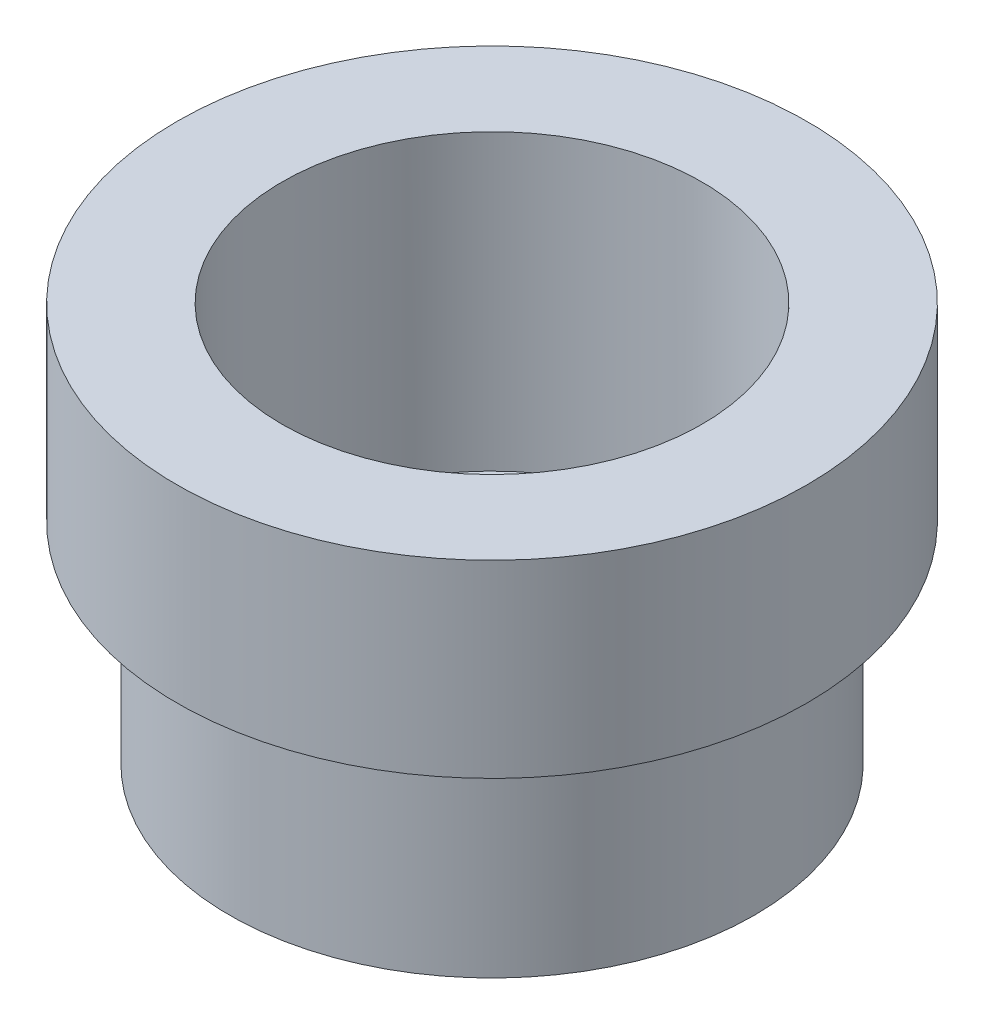
SolidWorks part; units mm, degrees
material "1060 Alloy"
ref_plane "Front" through (0, 0, 0) normal (0, 0, 1) x (1, 0, 0)
ref_plane "Top" through (0, 0, 0) normal (0, 1, 0) x (1, 0, 0)
ref_plane "Right" through (0, 0, 0) normal (1, 0, 0) x (0, 0, -1)
sketch "Sketch1" plane through (0, 0, 0) normal (0, 0, 1) x (1, 0, 0)
  line L0 (0, 0) -> (25, 0)
  line L1 (25, 0) -> (25, 20)
  line L2 (25, 20) -> (30, 20)
  line L3 (30, 20) -> (30, 38)
  line L6 (30, 38) -> (0, 38)
  line L7 (0, 38) -> (0, 0)
  dimension "D1" = 18
  dimension "D2" = 20
  dimension "D3" = 30
  dimension "D4" = 25
revolve "Revolve1" add sketch "Sketch1" angle 360 about L7
sketch "Sketch3" plane through (0, 38, 0) normal (0, 1, 0) x (1, 0, 0)
  circle A0 centre (0, 0) radius 10
  dimension "D1" = 20
extrude "bore through" cut sketch "Sketch3" against normal through all
sketch "Sketch5" plane through (0, 38, 0) normal (0, 1, 0) x (1, 0, 0)
  circle A0 centre (0, 0) radius 20
  dimension "D1" = 40
extrude "center cavity" cut sketch "Sketch5" against normal offset from surface (28 mm away) 10 up to face at (0, 0, 10)
sketch "m4 pattern alignment" plane through (0, 10, 0) normal (0, 1, 0) x (1, 0, 0)
  circle A0 centre (0, 0) radius 15 construction
  circle A1 centre (0, 15) radius 2.15
  point P3 (0, 15)
  point P4 (12.9904, 7.5)
  point P7 (12.9904, -7.5)
  point P8 (0, -15)
  point P9 (-12.9904, -7.5)
  point P10 (-12.9904, 7.5)
  point P11 (0, 0)
  dimension "D1" = 30
  dimension "D3" = 4.3
  dimension "D2" = 6
extrude "Cut-Extrude1" cut sketch "m4 pattern alignment" against normal through all
pattern_circular "CirPattern1" count 6 over 360 about axis through (0, 10, 0) along (0, -1, 0) of "Cut-Extrude1"
sketch "Sketch7" plane through (0, 10, 0) normal (0, 1, 0) x (1, 0, 0)
  circle A0 centre (0, 15) radius 4
extrude "Cut-Extrude2" cut sketch "Sketch7" against normal blind 4
pattern_circular "CirPattern2" count 6 over 360 about axis through (0, 10, 0) along (0, -1, 0) of "Cut-Extrude2"
equation "\"D1\"= \"motor mount plate thickness\""
equation "\"coupler motor shaft hole ID\"= 8mm"
equation "\"coupler OD\"= 17mm"
equation "\"coupler length\"= 25mm"
equation "\"square plate bolt pattern diameter\"= 3.5in"
equation "\"motor mount m4 screw hole diameter\"= 4mm"
equation "\"motor mount m4 head diameter\"= 7.25mm"
equation "\"motor mount m4 head depth\"= 4mm"
equation "\"motor mount plate thickness\"= 8mm + \"motor mount m4 head depth\""
equation "\"motor shaft pride\"= 32mm"
equation "\"motor mount m4 pattern diamater\"= 30mm"
equation "\"motor OD\"= 64mm"
equation "\"square plate bolt bore\"= \"m8 clearance\""
equation "\"square plate bolt head diameter\"= 13.5mm"
equation "\"motor to bearing plate distance\"= \"motor shaft pride\" + 2mm +\"coupler length\"/2"
equation "\"motor mount center bore\"= \"coupler OD\"+ 4mm"
equation "\"motor mount post radius\"= ( 3 * \"square plate bolt bore\" ) / 2"
equation "\"motor shaft diameter\"= 8mm"
equation "\"D1\"= 20mm"
equation "\"z\"= 8\t\t\t\t'number of blades"
equation "\"de\"= 0.43in\t\t\t'entrance eye diameter"
equation "\"de_length\"= 4mm\t\t'entrance eye consistent length"
equation "\"d_exit\"= 0.18in \t\t'throat aka d1"
equation "\"d2\"= 2.1in \t\t\t'outer diameter of the impeller"
equation "\"b2\"= .2in\t\t\t'tip height from disc surface at d2; slightly higher than d_exit"
equation "\"theta\"= 12\t\t\t'angle of blades from inner to outer "
equation "\"ae\"= 3.14*(\"de\"^2)/4\t\t'entrance eye area'"
equation "\"ce\"= 3.14*\"de\"\t\t'entrance eye circumference"
equation "\"av_ratio\"= .325\t\t'ratio of av/ae at N_s of 470, range is .275 to .375, .325 ideal. High ratio means bigger area means smaller blades"
equation "\"av\"= \"ae\"*\"av_ratio\"\t\t'area between just two blades"
equation "\"min blade thickness\"= .15in"
equation "\"diffuser cartridge OD\"=.75in"
equation "\"diffuser flange bolt pattern diameter\"= 1.4in"
equation "\"bearing OD\"= 30mm"
equation "\"bearing ID\"= 10mm"
equation "\"bearing depth\"= 9mm"
equation "\"bearing outer race thickness\"= 1mm"
equation "\"bearing inner race thickness\"= 1mm"
equation "\"bearing bore\"= \"bearing depth\" + 1mm"
equation "\"lower seal OD\"= .917in\t\t'this is https://www.mcmaster.com/#9281k121/=174001b"
equation "\"lower seal ID\"= .375in"
equation "\"lower seal depth\"= .625in + .218in"
equation "\"lower seal bore\"= \"lower seal depth\" + 1mm"
equation "\"upper seal OD\"= 1.125in\t'this is https://www.mcmaster.com/#5154t33/=173zuau, needs to be visually inspected before machining!"
equation "\"upper seal ID\"= 0.625in"
equation "\"upper seal depth\"= .25in\t'aka height; these values need to be confirmed by inspection!! We may want to compress the height."
equation "\"upper seal bore\"= \"upper seal depth\" + 1mm"
equation "\"big o-ring thickness\"= .139in"
equation "\"big o-ring OD\"= 2.734in"
equation "\"big o-ring ID\"= 3.012in"
equation "\"big o-ring groove depth\"= \"big o-ring thickness\"*4/5"
equation "\"impeller upper clearance\"= .5mm"
equation "\"impeller horizontal clearance\"= (\"d2\"*1.15 - \"d2\")/2 \t\t'clearance based on D2-D3 ratio for circular volute, ranges 1.15 to 1.2"
equation "\"impeller bottom clearance\"= .5mm"
equation "\"impeller base thickness\"= 2mm"
equation "\"impeller dowel diameter\"= 2mm"
equation "\"impeller bolt head depth\"= 4mm"
equation "\"impeller bolt stop depth\"= 3mm"
equation "\"impeller shaft bore depth\"= 12mm"
equation "\"impeller shaft bore\"= 8mm"
equation "\"impeller boss depth\"= \"impeller shaft bore depth\"+\"impeller bolt stop depth\"+\"impeller bolt head depth\"-\"impeller base thickness\""
equation "\"impeller boss diameter\"= \"upper seal ID\""
equation "\"impeller dowel length\"= 2mm*2 + \"impeller shaft bore\""
equation "\"square plate bolt head depth\"= 8mm"
equation "\"bearing plate stop ID\"= \"bearing OD\" - 4mm"
equation "\"bearing plate stop depth\"= 3mm"
equation "\"lower seal plate lip depth\"= 2mm"
equation "\"lower seal plate lip ID\"= \"lower seal OD\" - 3mm"
equation "\"lower seal plate thickness\"= \"lower seal plate lip depth\" + \"lower seal bore\""
equation "\"shaft coupler section diameter\"= 8mm"
equation "\"shaft coupler section length\"= \"motor to bearing plate distance\" - \"motor shaft pride\" - 2mm"
equation "\"shaft bearing section diameter\"= \"bearing ID\""
equation "\"shaft bearing section length\"= \"bearing plate stop depth\" + \"bearing depth\""
equation "\"shaft bearing stop diameter\"= \"bearing ID\" + 4mm"
equation "\"shaft bearing stop length\"= 3mm"
equation "\"shaft lower seal section diameter\"= \"lower seal ID\""
equation "\"shaft lower seal section length\"= \"lower seal plate thickness\" + 1mm"
equation "\"shaft impeller section diameter\"= \"impeller shaft bore\""
equation "\"upper seal plate lip ID\"= \"upper seal OD\" - 3mm"
equation "\"upper seal plate riser\"= 6.59mm \t\t'this number needs to be read from the housing file"
equation "\"upper seal plate pressure hole diameter\"= .125in\t'this is 1/8 drill "
equation "\"upper seal plate pressure tap diameter\"= .328125in \t'this is 21/64 drill for a 1/8 ANPT tap"
equation "\"upper seal plate pressure tap grip\"= 5mm\t\t'this is the area around the tap so it doesn't crack"
equation "\"upper seal plate pressure tap depth\"= 12mm"
equation "\"impeller cavity diameter\"= 2 * \"impeller horizontal clearance\" + \"d2\" \t\t\t\t\t\t\t\t\t'called D3 analytically"
equation "\"impeller cavity outer height\"= \"impeller bottom clearance\" + \"impeller upper clearance\" + \"impeller base thickness\" + \"b2\" \t\t'this is height at impeller diameter d2, not at d3"
equation "\"impeller housing diameter\"= 4.5in"
equation "\"impeller housing bolt count\"= 8"
equation "\"impeller housing bolt pattern diameter\"= 3.5in"
equation "\"impeller housing threaded inlet diameter\"= 0.71875in \t'this is the 23/32 drill size for 1/2 NPT fitting https://www.mcmaster.com/#50715k269/=176pljy"
equation "\"impeller housing threaded inlet depth\"= .6in"
equation "\"impeller housing exit threaded diameter\"= 0.515625in \t\t'this is the 33/64 drill size for 9/16-18 fitting, expecting swagelok SS-8FK0-1-6STH fitting"
equation "\"impeller housing exit threaded depth\"= 10mm"
equation "\"impeller housing diffuser conical angle\"=10"
equation "\"impeller housing diffuser tangent angle\"=5"
equation "\"impeller housing diffuser final diameter\"= .38in\t\t'aka d2'"
equation "\"impeller housing outlet grip\"= 5mm"
equation "\"end mill size\"= 0.375in\t'for 3/8 endmill"
equation "\"m4 clearance\"= 0.171875in \t'this is 11/64 bit for 4.36mm"
equation "\"m4 tap\"= 0.125in\t\t'this is 1/8 bit for 3.17mm"
equation "\"m4 head bore diameter\"= 7.5mm"
equation "\"m4 head bore depth\"= 5mm\t'actual is ~4mm"
equation "\"m6 clearance\"= 0.234375in\t'this is 15/64 bit = 5.95mm, could use 6mm bit, B bit for 6.04mm or 1/4 bit for 6.35mm"
equation "\"m6 tap\"= 5mm\t\t\t'5mm is appropriate, could use 13/64 or #5,6,7"
equation "\"m6 head bore diameter\"= 11mm\t\t"
equation "\"m6 head bore depth\"= 7mm\t'actual is 6mm"
equation "\"m8 clearance\"= 0.3125in\t'this is 5/16in for 7.93mm, could use 8mm, O,P, or 21/64"
equation "\"m8 tap\"= 0.265625in\t\t'this is 17/64 for 6.746875mm"
equation "\"m8 head bore diameter\"= 14mm"
equation "\"m8 head bore depth\"= 9mm\t'actual is 8mm"
